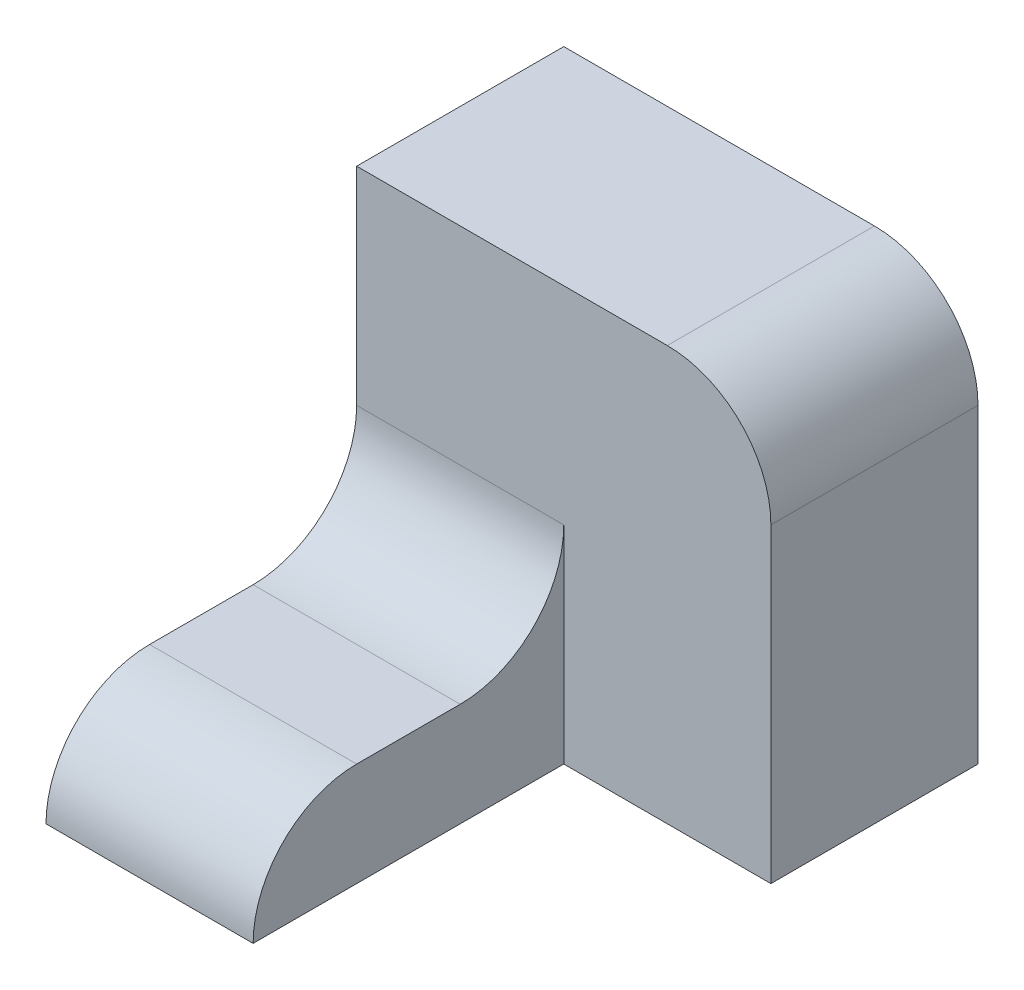
SolidWorks part; units mm, degrees
ref_plane "Front Plane" through (0, 0, 0) normal (0, 0, 1) x (1, 0, 0)
ref_plane "Top Plane" through (0, 0, 0) normal (0, 1, 0) x (1, 0, 0)
ref_plane "Right Plane" through (0, 0, 0) normal (1, 0, 0) x (0, 0, -1)
sketch "Sketch1" plane through (0, 0, 0) normal (0, 0, 1) x (1, 0, 0)
  line L1 (-30, -10) -> (-10, -10)
  line L2 (-10, -10) -> (-10, 0)
  line L3 (-10, 0) -> (-30, 0)
  line L4 (-30, 0) -> (-30, -10)
  dimension "D1" = 20
  dimension "Width" = 10
extrude "Boss-Extrude1" add sketch "Sketch1" along normal blind 30
sketch "Sketch2" plane through (0, 0, 0) normal (0, 0, 1) x (1, 0, 0)
  line L1 (-30, -10) -> (10, -10)
  line L2 (10, -10) -> (10, 30)
  line L3 (10, 30) -> (-30, 30)
  line L4 (-30, 30) -> (-30, -10)
  dimension "D1" = 40
  dimension "Width" = 40
extrude "Boss-Extrude2" add sketch "Sketch2" against normal blind 20
fillet "Fillet1" radius 10 3 edges at (-20, 0, 0) (10, 30, -10) (-20, 0, 30)
